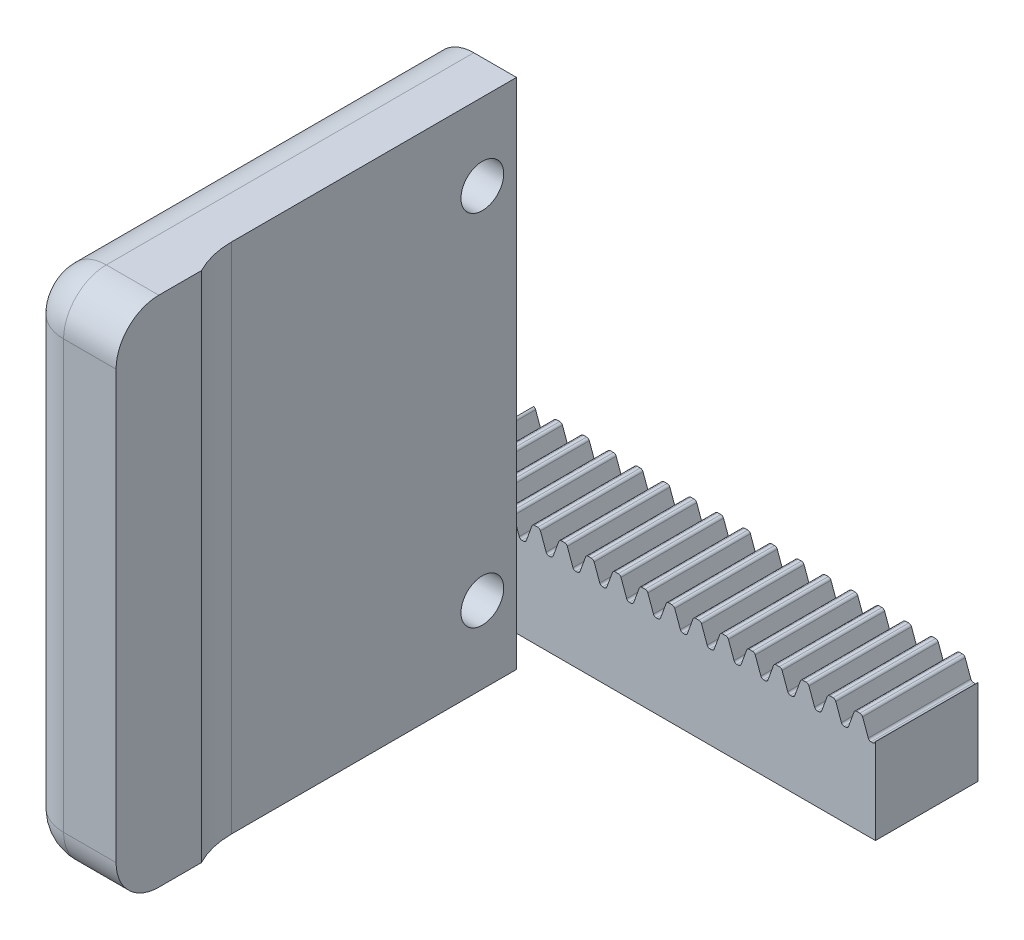
SolidWorks part; units mm, degrees
other "Markup1"
sketch "Sketch7" plane through (-50, -9.66, 16) normal (-0.9886, -0.1404, 0.0537) x (0.0542, 0, 0.9985)
ref_plane "Front Plane" through (0, 0, 0) normal (0, 0, 1) x (1, 0, 0)
ref_plane "Top Plane" through (0, 0, 0) normal (0, 1, 0) x (1, 0, 0)
ref_plane "Right Plane" through (0, 0, 0) normal (1, 0, 0) x (0, 0, -1)
sketch "Sketch1" plane through (0, 0, 0) normal (0, 0, 1) x (1, 0, 0)
  line L0 (-50, 6) -> (-50, -6) construction
  line L1 (-50, -6) -> (50, -6) construction
  line L2 (50, -6) -> (50, 6) construction
  line L4 (0, 6) -> (0, -6) construction
  line L5 (-50, 5) -> (50, 5) construction
  line L6 (-47.5453, 6) -> (-46.7025, 6) construction
  line L7 (-46.7025, 6) -> (-45.8835, 3.75) construction
  line L8 (-47.5453, 6) -> (-48.3643, 3.75) construction
  line L9 (-48.3643, 3.75) -> (-45.8835, 3.75) construction
  line L10 (-47.1239, 6) -> (-47.1239, 3.75) construction
  line L11 (-50, 0) -> (-40.8407, 0) construction
  line L12 (50, 0) -> (40.8407, 0) construction
  point P15 (-43.9823, 6)
  point P16 (-15.5, -6)
  point P17 (-46.3385, 5)
  point P18 (-47.9093, 5)
  point P21 (-0.5, -6)
  dimension "Length" = 100
  dimension "Height" = 12
  dimension "Approximate Number of Teeth" = 31
  dimension "Pressure Angle" = 20
  dimension "Circular Pitch" = 3.1416
  dimension "Addendum" = 1
  dimension "Dedendum" = 1.25
  dimension "Circular Tooth Thickness" = 1.5708
  dimension "Module" = 1
  dimension "Rack Length" = 94.2478
  dimension "D1" = 6.2832
sketch "Sketch2" plane through (0, 0, 0) normal (1, 0, 0) x (0, 0, -1)
  line L0 (-6, 0) -> (6, 0) construction
  dimension "Face Width" = 12
sketch "Sketch3" plane through (0, 0, 0) normal (0, 0, 1) x (1, 0, 0)
  line L1 (-50, 6) -> (50, 6)
  line L2 (-50, 6) -> (-50, -6)
  line L3 (-50, -6) -> (50, -6)
  line L4 (50, 6) -> (50, -6)
extrude "Boss-Extrude1" add sketch "Sketch3" against normal up to vertex (6 mm away) and the other way up to vertex (6 mm away) up to point (0, 0, -6) other way up to point (0, 0, 6)
sketch "Sketch4" plane through (0, 0, 0) normal (0, 0, 1) x (1, 0, 0)
  line L0 (-47.1239, 6) -> (-43.9823, 6) construction
  line L9 (-45.5531, 6) -> (-45.5531, 3.75)
  line L10 (-45.5531, 3.75) -> (-45.8835, 3.75)
  line L11 (-45.8835, 3.75) -> (-46.7025, 6)
  line L12 (-46.7025, 6) -> (-45.5531, 6)
  line L13 (-47.5453, 6) -> (-48.3643, 3.75)
  line L14 (-48.3643, 3.75) -> (-48.6947, 3.75)
  line L15 (-48.6947, 3.75) -> (-48.6947, 6)
  line L16 (-48.6947, 6) -> (-47.5453, 6)
  line L17 (50, 6) -> (-50, 6) construction
  line L18 (-47.5453, 6) -> (-47.3104, 6)
  line L19 (-46.9374, 6) -> (-46.7025, 6)
  arc A0 (-48.5992, 3.75) -> (-48.2839, 3.9708) centre (-48.5992, 4.0855) ccw
  arc A1 (-45.9639, 3.9708) -> (-45.6486, 3.75) centre (-45.6486, 4.0855) ccw
  arc A2 (-47.6257, 5.7792) -> (-47.3104, 6) centre (-47.3104, 5.6645) cw
  arc A3 (-46.9374, 6) -> (-46.6221, 5.7792) centre (-46.9374, 5.6645) cw
  dimension "D1" = 0.3355
extrude "Cut-Extrude1" cut sketch "Sketch4" against normal through all both and the other way through all contours L14 A0 L13 L16 L15 | L13 A2 L18 | L19 A3 L11 | L11 A1 L10 L9 L12 region at (-45.9615, 5.0903, 0) region at (-46.7355, 5.9529, 0) region at (-47.5123, 5.9529, 0) region at (-48.2863, 5.0903, 0)
pattern_linear "LPattern1" count 32 spacing 3.1416 along (1, 0, 0) count 2 spacing 3.1416 along (-1, 0, 0) of "Cut-Extrude1"
sketch "Drawing Refernce 1" plane through (0, 0, 6) normal (0, 0, 1) x (1, 0, 0)
  line L0 (-50, 0) -> (50, 0) construction
  point P6 (-35, 0)
  point P7 (-27.5, 0)
  point P8 (35, 0)
  dimension "D1" = 15
  dimension "D2" = 22.5
  dimension "D3" = 15
sketch "Sketch5" plane through (0, 0, 6) normal (0, 0, 1) x (1, 0, 0)
  line L0 (2, -6) -> (2, 23.2722) construction
  line L1 (-50, -6) -> (50, -6) construction
  line L2 (-50, 5.9906) -> (-50, -6) construction
  line L8 (2, -6) -> (50.3789, -6)
  line L9 (2, -6) -> (2, 6.3802)
  line L10 (2, 6.3802) -> (50.3789, 6.3802)
  line L11 (50.3789, -6) -> (50.3789, 6.3802)
  dimension "D1" = 52
extrude "Cut-Extrude2" cut sketch "Sketch5" against normal through all
sketch "Sketch6" plane through (0, 0, 6) normal (0, 0, 1) x (1, 0, 0)
  line L0 (-50, -6) -> (2, -6) construction
  line L1 (-50, -9.66) -> (-40, -9.66)
  line L2 (-50, -9.66) -> (-50, 50.34)
  line L3 (-50, 50.34) -> (-40, 50.34)
  line L4 (-40, -9.66) -> (-40, 50.34)
  line L5 (-50, 5.9906) -> (-50, -6) construction
  dimension "D1" = 10
  dimension "D2" = 3.66
  dimension "D3" = 60
extrude "Boss-Extrude2" add sketch "Sketch6" along normal blind 8
sketch "Sketch8" plane through (-50, 0, 0) normal (-1, 0, 0) x (0, 0, 1)
  line L1 (14, 50.34) -> (14, -9.66) construction
  line L2 (14, -9.66) -> (6, -9.66) construction
  line L3 (14, 50.34) -> (6, 50.34) construction
  circle A0 centre (10, 41.34) radius 2.5
  circle A1 centre (10, -0.66) radius 2.5
  dimension "D1" = 5
  dimension "D2" = 5
  dimension "D3" = 4
  dimension "D4" = 4
  dimension "D5" = 9
  dimension "D6" = 9
extrude "Cut-Extrude3" cut sketch "Sketch8" against normal through all
sketch "Sketch9" plane through (0, 0, 14) normal (0, 0, 1) x (1, 0, 0)
  line L0 (-40, -9.66) -> (-40, 50.34) construction
  line L1 (-50, 50.34) -> (-38.86, 50.34)
  line L2 (-50, 50.34) -> (-50, -9.66)
  line L3 (-50, -9.66) -> (-38.86, -9.66)
  line L4 (-38.86, 50.34) -> (-38.86, -9.66)
  dimension "D1" = 1.14
extrude "Boss-Extrude3" add sketch "Sketch9" along normal blind 40
sketch "Sketch10" plane through (0, -9.66, 0) normal (0, -1, 0) x (1, 0, 0)
  line L0 (-50, 44) -> (-38.86, 44) construction
  line L1 (-50, 54) -> (-50, 6) construction
  line L2 (-38.86, 54) -> (-38.86, 14) construction
  line L3 (-50, 54) -> (-38.86, 54) construction
  line L5 (-38.86, 44) -> (-38.86, 14)
  line L6 (-38.86, 14) -> (-40, 14)
  line L7 (-40, 14) -> (-40, 44)
  line L8 (-40, 44) -> (-38.86, 44)
  dimension "D1" = 10
extrude "Cut-Extrude4" cut sketch "Sketch10" against normal through all both
fillet "Fillet2" radius 5 5 edges at (-44.43, 50.34, 54) (-44.43, -9.66, 54) (-50, 20.34, 54) (-50, 50.34, 30) (-50, -9.66, 30)
fillet "Fillet3" radius 10 1 edges at (-40, 20.34, 44)
equation "\"Diametral Pitch\"= 1 / \"Module\""
equation "\"Pressure Angle\"=20"
equation "\"Dedendum\"= 1.25 / \"Diametral Pitch\""
equation "\"Addendum\"= 1 / \"Diametral Pitch\""
equation "\"WorkingDepth\"= 2 / \"Diametral Pitch\""
equation "\"WholeDepth\"= 2.25 / \"Diametral Pitch\""
equation "\"Clearance\"= 0.25 / \"Diametral Pitch\""
equation "\"ToothThickness\"= ( pi / 2 ) / \"Diametral Pitch\""
equation "\"CircularPitch\"= pi / \"Diametral Pitch\""
equation "\"Fillet\"= \"Clearance\" * cos ( \"Pressure Angle\" ) * tan ( ( 90 + \"Pressure Angle\" ) / 2 )"
equation "\"Module\"= 1"
equation "\"Addendum@Sketch1\"=\"Addendum\""
equation "\"Pressure Angle@Sketch1\"=\"Pressure Angle\""
equation "\"Dedendum@Sketch1\"=\"Dedendum\""
equation "\"Circular Pitch@Sketch1\"=\"CircularPitch\""
equation "\"Circular Tooth Thickness@Sketch1\"=\"ToothThickness\""
equation "\"Module@Sketch1\"=\"Module\""
equation "\"Approximate Number of Teeth@Sketch1\" = int ( \"Length@Sketch1\" /  ( 2 * \"Circular Tooth Thickness@Sketch1\" )  ) "
equation "\"Rack Length@Sketch1\" = \"Circular Pitch@Sketch1\" *  ( \"Approximate Number of Teeth@Sketch1\" - 1 ) "
equation "\"D3@LPattern1\"=\"CircularPitch\""
equation "\"D1@LPattern1\"=\"Approximate Number of Teeth@Sketch1\"+1"
equation "\"D1@Sketch1\"=\"Circular Pitch@Sketch1\"*2"
equation "\"D1@Sketch4\"=\"Fillet\""
equation "\"D4@LPattern1\"=\"CircularPitch\""
equation "\"D2@Drawing Refernce 1\"=\"D1@Drawing Refernce 1\"*1.5"
equation "\"D3@Drawing Refernce 1\"=\"D1@Drawing Refernce 1\""
